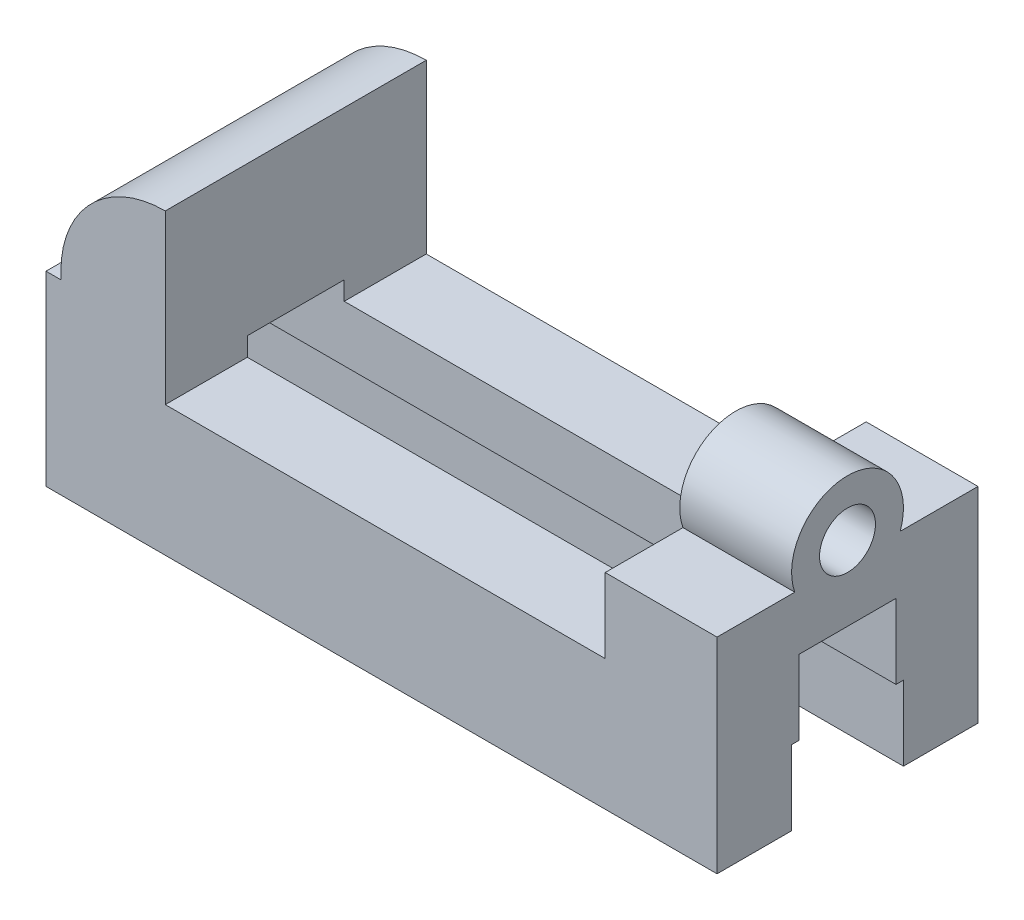
SolidWorks part; units mm, degrees
ref_plane "Front Plane" through (0, 0, 0) normal (0, 0, 1) x (1, 0, 0)
ref_plane "Top Plane" through (0, 0, 0) normal (0, 1, 0) x (1, 0, 0)
ref_plane "Right Plane" through (0, 0, 0) normal (1, 0, 0) x (0, 0, -1)
sketch "Sketch1" plane through (0, 0, 0) normal (0, 0, 1) x (1, 0, 0)
  line L0 (0, 0) -> (0, 45927.9878) construction
  line L1 (0, 0) -> (45927.9878, 0) construction
  line L2 (0, 0) -> (180, 0)
  line L3 (180, 0) -> (180, 55)
  line L4 (180, 55) -> (150, 55)
  line L5 (150, 55) -> (150, 35)
  line L6 (150, 35) -> (32, 35)
  line L7 (32, 35) -> (32, 80)
  line L8 (32, 80) -> (31.9999, 80)
  line L9 (4, 52.0001) -> (4, 50)
  line L10 (4, 50) -> (0, 50)
  line L11 (0, 50) -> (0, 0)
  arc A0 (31.9999, 80) -> (4, 52.0001) centre (31.9999, 52.0001) ccw
  point P17 (4, 80)
  dimension "D9" = 27.9999
  dimension "D1" = 180
  dimension "D2" = 30
  dimension "D3" = 55
  dimension "D4" = 35
  dimension "D5" = 80
  dimension "D6" = 28
  dimension "D7" = 4
  dimension "D8" = 50
extrude "Boss-Extrude1" add sketch "Sketch1" against normal blind 70
sketch "Sketch2" plane through (0, 0, 0) normal (-1, 0, 0) x (0, 0, 1)
  line L0 (-50, 0) -> (-50, 20)
  line L1 (-70, 0) -> (0, 0) construction
  line L2 (-50, 20) -> (-48, 20)
  line L3 (-48, 20) -> (-48, 40)
  line L4 (-48, 40) -> (-22, 40)
  line L5 (-22, 40) -> (-22, 20)
  line L6 (-22, 20) -> (-20, 20)
  line L7 (-20, 20) -> (-20, 0)
  line L8 (-70, 50) -> (-70, 0) construction
  line L9 (0, 50) -> (0, 0) construction
  line L10 (-50, 0) -> (-20, 0)
  dimension "D1" = 20
  dimension "D2" = 20
  dimension "D3" = 20
  dimension "D4" = 20
  dimension "D5" = 20
  dimension "D6" = 26
extrude "Cut-Extrude3" cut sketch "Sketch2" against normal blind 196
sketch "Sketch3" plane through (150, 0, 0) normal (-1, 0, 0) x (0, 0, 1)
  line L0 (-70, 35) -> (-48, 35) construction
  line L1 (-22, 40) -> (-48, 40) construction
  circle A0 centre (-35, 60) radius 7.5
  circle A1 centre (-35, 60) radius 15
  point P7 (-35, 40)
  dimension "D1" = 15
  dimension "D2" = 30
  dimension "D3" = 25
  dimension "D4" = 0
ref_plane "Plane1" through (180, 0, 0) normal (-1, 0, 0) x (0, 0, 1)
sketch "Sketch5" plane through (180, 0, 0) normal (-1, 0, 0) x (0, 0, 1)
  line L0 (-29.4098, 55) -> (-40.5902, 55)
  line L1 (-70, 55) -> (0, 55) construction
  circle A0 centre (-35, 60) radius 7.5
  circle A1 centre (-35, 60) radius 15
extrude "Boss-Extrude3" add sketch "Sketch5" along normal blind 30 contours A1 A0 region at (180, 60, -49.5757)
extrude "Cut-Extrude4" cut sketch "Sketch5<3>" along normal blind 30 contours L0 A0 region at (180, 53.9842, -35)
sketch "Sketch5<3>" plane through (180, 0, 0) normal (-1, 0, 0) x (0, 0, 1) same geometry as "Sketch5"
